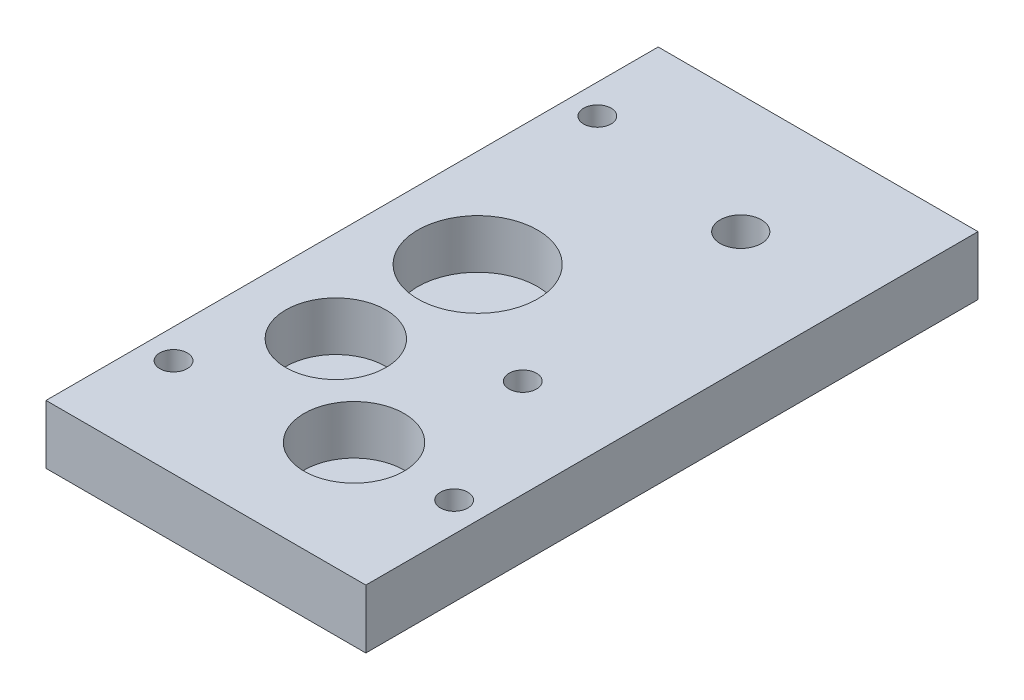
SolidWorks part; units mm, degrees
ref_plane "前视基准面" through (0, 0, 0) normal (0, 0, 1) x (1, 0, 0)
ref_plane "上视基准面" through (0, 0, 0) normal (0, 1, 0) x (1, 0, 0)
ref_plane "右视基准面" through (0, 0, 0) normal (1, 0, 0) x (0, 0, -1)
other "Configuration Table"
sketch "草图1" plane through (0, 0, 0) normal (0, 1, 0) x (1, 0, 0)
  line L1 (-5, 14.2) -> (11.3, 14.2)
  line L2 (-5, 14.2) -> (-5, -17)
  line L3 (-5, -17) -> (11.3, -17)
  line L4 (11.3, 14.2) -> (11.3, -17)
  circle A0 centre (0, 0) radius 3.05
  circle A6 centre (4.7, -11) radius 2.55
  circle A10 centre (-0.3371, -6.8918) radius 2.55
  circle A11 centre (5.2565, 8.1523) radius 1.05
  point P11 (0, 0)
  point P14 (0, 0)
  dimension "D5" = 6.1
  dimension "D6" = 5.1
  dimension "D9" = 5.1
  dimension "D10" = 2.1
  dimension "D1" = 14.2
  dimension "D2" = 5
  dimension "D3" = 11.3
  dimension "D4" = 17
extrude "凸台-拉伸1" add sketch "草图1" along normal blind 3 contours L2 L3 L4 L1
extrude "切除-拉伸1" cut sketch "草图1<3>" against normal blind 2.5 from surface contours A0 | A6 | A10 | A11 starting at face at (3.15, 3, 1.4)
sketch "草图1<3>" plane through (0, 0, 0) normal (0, 1, 0) x (1, 0, 0) same geometry as "草图1"
sketch "草图2" plane through (0, 0, 0) normal (0, -1, 0) x (1, 0, 0)
  circle A0 centre (9.8, 11) radius 1
  circle A1 centre (9.8, 11) radius 0.7
  circle A2 centre (-3.5, 12) radius 1
  circle A3 centre (-3.5, 12) radius 0.7
  circle A4 centre (6.3, 4) radius 1
  circle A5 centre (6.3, 4) radius 0.7
  circle A6 centre (-3.5, -9.6) radius 1
  circle A7 centre (-3.5, -9.6) radius 0.7
  dimension "D1" = 1.4
  dimension "D2" = 2
extrude "切除-拉伸2" cut sketch "草图2" against normal blind 1.5 contours A2 | A0 | A4 | A6
extrude "切除-拉伸3" cut sketch "草图2<3>" against normal through all contours A7 | A1 | A3 | A5
sketch "草图2<3>" plane through (0, 0, 0) normal (0, -1, 0) x (1, 0, 0) same geometry as "草图2"
